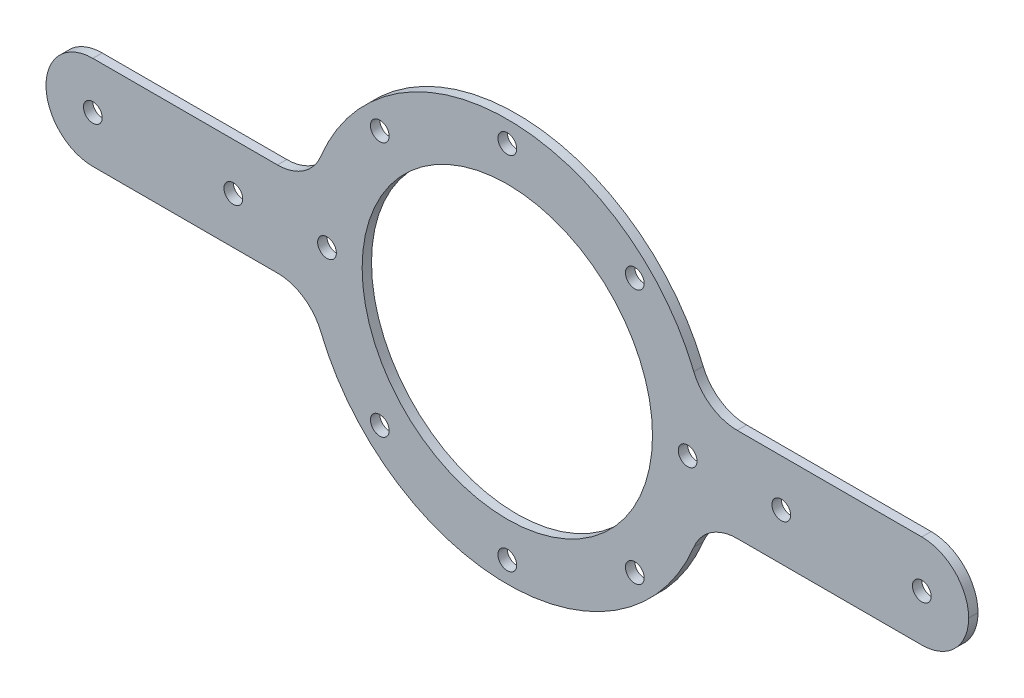
SolidWorks part; units mm, degrees
ref_plane "Front Plane" through (0, 0, 0) normal (0, 0, 1) x (1, 0, 0)
ref_plane "Top Plane" through (0, 0, 0) normal (0, 1, 0) x (1, 0, 0)
ref_plane "Right Plane" through (0, 0, 0) normal (1, 0, 0) x (0, 0, -1)
sketch "Sketch1" plane through (0, 0, 0) normal (0, 0, 1) x (1, 0, 0)
  line L0 (98.5, 0) -> (18.5, 0) construction
  line L1 (-41.821, 10) -> (-98.5, 10)
  line L2 (-98.5, 10) -> (-98.5, -10)
  line L3 (-98.5, -10) -> (-41.821, -10)
  line L4 (41.821, 10) -> (98.5, 10)
  line L5 (98.5, 10) -> (98.5, -10)
  line L6 (98.5, -10) -> (41.821, -10)
  line L7 (-43, 0) -> (-98.5, 0) construction
  circle A0 centre (0, 0) radius 31
  arc A1 (41.821, 10) -> (-41.821, 10) centre (0, 0) ccw
  arc A2 (-41.821, -10) -> (41.821, -10) centre (0, 0) ccw
  circle A3 centre (0, 38.5) radius 2
  circle A4 centre (27.2236, 27.2236) radius 2
  circle A5 centre (38.5, 0) radius 2
  circle A6 centre (27.2236, -27.2236) radius 2
  circle A7 centre (0, -38.5) radius 2
  circle A8 centre (-27.2236, -27.2236) radius 2
  circle A9 centre (-38.5, 0) radius 2
  circle A10 centre (-27.2236, 27.2236) radius 2
  circle A11 centre (-58.5, 0) radius 2
  circle A12 centre (-88.5, 0) radius 2
  circle A13 centre (58.5, 0) radius 2
  circle A14 centre (88.5, 0) radius 2
  point P7 (0, 0)
  point P19 (-98.5, 0)
  point P35 (0, 0)
  dimension "D1" = 4
  dimension "D3" = 62
  dimension "D4" = 43
  dimension "D7" = 4
  dimension "D2" = 38.5
  dimension "D6" = 20
  dimension "D8" = 20
  dimension "D9" = 30
  dimension "D10" = 20
  dimension "D11" = 30
  dimension "D12" = 10
  dimension "D13" = 10
  dimension "D5" = 8
extrude "Boss-Extrude1" add sketch "Sketch1" along normal mid plane 2
fillet "Fillet1" radius 10 8 edges at (98.5, -10, 0) (98.5, 10, 0) (41.821, -10, 0) (41.821, 10, 0) (-41.821, -10, 0) (-98.5, -10, 0) (-98.5, 10, 0) (-41.821, 10, 0)
